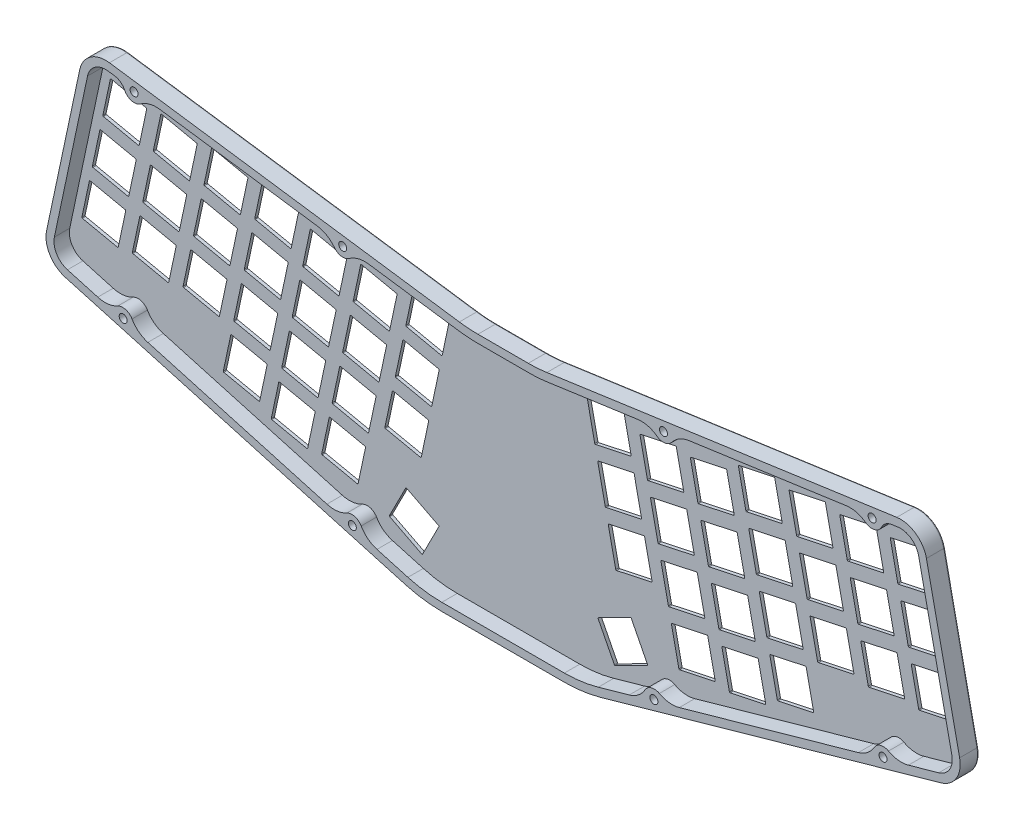
SolidWorks part; units mm, degrees
ref_plane "Front Plane" through (0, 0, 0) normal (0, 0, 1) x (1, 0, 0)
ref_plane "Top Plane" through (0, 0, 0) normal (0, 1, 0) x (1, 0, 0)
ref_plane "Right Plane" through (0, 0, 0) normal (1, 0, 0) x (0, 0, -1)
sketch "Model" plane through (0, 0, 0) normal (0, 0, 1) x (1, 0, 0)
  line L0 (325.3126, 39.9244) -> (319.5653, 66.9637)
  line L1 (325.3126, 39.9244) -> (332.0603, 8.179)
  line L2 (322.3782, 39.3007) -> (316.6308, 66.34)
  line L3 (322.3782, 39.3007) -> (329.1259, 7.5553)
  line L4 (306.4458, 71.4818) -> (308.8024, 71.8155)
  line L5 (13.8071, 71.4818) -> (11.4504, 71.8155)
  line L6 (-5.0598, 39.9244) -> (-11.8075, 8.179)
  line L7 (-2.1254, 39.3007) -> (-8.8731, 7.5553)
  line L8 (-5.0598, 39.9244) -> (0.6876, 66.9637)
  line L9 (-2.1254, 39.3007) -> (3.622, 66.34)
  line L10 (26.3327, -9.1816) -> (48.3039, -15.3856)
  line L11 (48.3039, -15.3856) -> (93.7705, -28.2242)
  line L12 (-3.9283, -0.6367) -> (7.4742, -3.8564)
  line L13 (90.0873, 60.6806) -> (30.9176, 69.0589)
  line L14 (210.7632, 57.9332) -> (177.0346, 53.1572)
  line L15 (169.604, 52.6338) -> (150.6488, 52.6338)
  line L16 (143.2182, 53.1572) -> (109.4896, 57.9332)
  line L17 (289.3352, 69.0589) -> (230.1656, 60.6806)
  line L18 (312.7787, -3.8564) -> (324.1811, -0.6367)
  line L19 (226.4824, -28.2242) -> (271.949, -15.3856)
  line L20 (271.949, -15.3856) -> (293.9202, -9.1816)
  line L21 (112.629, -33.5493) -> (124.2783, -36.8388)
  line L22 (137.0504, -38.6074) -> (160.1264, -38.6074)
  line L23 (160.1264, -38.6074) -> (183.2025, -38.6074)
  line L24 (195.9746, -36.8388) -> (207.6239, -33.5493)
  line L25 (169.604, 55.6338) -> (150.6488, 55.6338)
  line L26 (308.3818, 74.7858) -> (176.614, 56.1276)
  line L27 (272.7642, -18.2727) -> (324.9963, -3.5238)
  line L28 (196.7898, -39.7259) -> (272.7642, -18.2727)
  line L29 (160.1264, -41.6074) -> (183.2025, -41.6074)
  line L30 (137.0504, -41.6074) -> (160.1264, -41.6074)
  line L31 (47.4886, -18.2727) -> (123.463, -39.7259)
  line L32 (-4.7435, -3.5238) -> (47.4886, -18.2727)
  line L33 (143.6388, 56.1276) -> (11.8711, 74.7858)
  line L34 (196.5845, -32.4293) -> (202.5988, -29.3648)
  line L35 (190.1194, -20.2914) -> (196.2483, -32.32)
  line L36 (202.2573, -13.8263) -> (190.2287, -19.9552)
  line L37 (208.7224, -25.9641) -> (202.5935, -13.9355)
  line L38 (202.5988, -29.3648) -> (208.6131, -26.3004)
  line L39 (234.2278, -18.5408) -> (231.421, -5.3358)
  line L40 (220.8303, -21.6441) -> (234.0353, -18.8373)
  line L41 (217.7269, -8.2465) -> (220.5338, -21.4515)
  line L42 (231.1245, -5.1432) -> (217.9195, -7.95)
  line L43 (253.2284, -16.5467) -> (250.4216, -3.3417)
  line L44 (239.8309, -19.6501) -> (253.0359, -16.8433)
  line L45 (236.7276, -6.2525) -> (239.5344, -19.4575)
  line L46 (250.1251, -3.1492) -> (236.9201, -5.956)
  line L47 (210.4452, 1.9626) -> (207.6384, 15.1676)
  line L48 (197.0477, -1.1407) -> (210.2527, 1.6661)
  line L49 (193.9443, 12.2568) -> (196.7512, -0.9482)
  line L50 (207.3419, 15.3602) -> (194.1369, 12.5533)
  line L51 (206.4949, 20.5474) -> (203.6881, 33.7524)
  line L52 (193.0973, 17.4441) -> (206.3023, 20.2509)
  line L53 (189.994, 30.8416) -> (192.8008, 17.6366)
  line L54 (203.3916, 33.945) -> (190.1866, 31.1382)
  line L55 (202.5446, 39.1322) -> (199.7378, 52.3372)
  line L56 (189.147, 36.0289) -> (202.352, 38.8357)
  line L57 (186.0437, 49.4264) -> (188.8505, 36.2214)
  line L58 (199.4413, 52.5298) -> (186.2363, 49.723)
  line L59 (230.2775, 0.044) -> (227.4707, 13.249)
  line L60 (216.8799, -3.0593) -> (230.0849, -0.2525)
  line L61 (213.7766, 10.3383) -> (216.5834, -2.8667)
  line L62 (227.1742, 13.4416) -> (213.9692, 10.6348)
  line L63 (226.3272, 18.6288) -> (223.5204, 31.8338)
  line L64 (212.9296, 15.5255) -> (226.1346, 18.3323)
  line L65 (209.8263, 28.9231) -> (212.6331, 15.7181)
  line L66 (223.2239, 32.0264) -> (210.0189, 29.2196)
  line L67 (222.3769, 37.2136) -> (219.57, 50.4186)
  line L68 (208.9793, 34.1103) -> (222.1843, 36.9171)
  line L69 (205.876, 47.5079) -> (208.6828, 34.3029)
  line L70 (219.2735, 50.6112) -> (206.0685, 47.8044)
  line L71 (249.2781, 2.0381) -> (246.4713, 15.2431)
  line L72 (235.8806, -1.0653) -> (249.0856, 1.7416)
  line L73 (232.7772, 12.3323) -> (235.5841, -0.8727)
  line L74 (246.1748, 15.4356) -> (232.9698, 12.6288)
  line L75 (245.3278, 20.6229) -> (242.521, 33.8279)
  line L76 (231.9302, 17.5195) -> (245.1352, 20.3264)
  line L77 (228.8269, 30.9171) -> (231.6337, 17.7121)
  line L78 (242.2245, 34.0204) -> (229.0195, 31.2136)
  line L79 (241.3775, 39.2077) -> (238.5707, 52.4127)
  line L80 (227.9799, 36.1044) -> (241.1849, 38.9112)
  line L81 (224.8766, 49.5019) -> (227.6834, 36.2969)
  line L82 (238.2742, 52.6052) -> (225.0692, 49.7984)
  line L83 (271.2935, -10.151) -> (268.4867, 3.0539)
  line L84 (257.8959, -13.2544) -> (271.1009, -10.4476)
  line L85 (254.7926, 0.1432) -> (257.5994, -13.0618)
  line L86 (268.1901, 3.2465) -> (254.9852, 0.4397)
  line L87 (267.3431, 8.4338) -> (264.5363, 21.6387)
  line L88 (253.9456, 5.3304) -> (267.1506, 8.1372)
  line L89 (250.8423, 18.728) -> (253.6491, 5.523)
  line L90 (264.2398, 21.8313) -> (251.0348, 19.0245)
  line L91 (263.3928, 27.0186) -> (260.586, 40.2236)
  line L92 (249.9953, 23.9152) -> (263.2003, 26.722)
  line L93 (246.892, 37.3128) -> (249.6988, 24.1078)
  line L94 (260.2895, 40.4161) -> (247.0845, 37.6093)
  line L95 (259.4425, 45.6034) -> (256.6357, 58.8084)
  line L96 (246.045, 42.5) -> (259.2499, 45.3069)
  line L97 (242.9416, 55.8976) -> (245.7484, 42.6926)
  line L98 (256.3392, 59.0009) -> (243.1342, 56.1941)
  line L99 (286.4477, 9.9387) -> (283.6409, 23.1437)
  line L100 (273.0502, 6.8354) -> (286.2552, 9.6422)
  line L101 (269.9469, 20.2329) -> (272.7537, 7.0279)
  line L102 (283.3444, 23.3363) -> (270.1394, 20.5295)
  line L103 (282.4974, 28.5235) -> (279.6906, 41.7285)
  line L104 (269.0999, 25.4202) -> (282.3049, 28.227)
  line L105 (265.9965, 38.8177) -> (268.8033, 25.6128)
  line L106 (279.3941, 41.9211) -> (266.1891, 39.1143)
  line L107 (278.5471, 47.1083) -> (275.7403, 60.3133)
  line L108 (265.1495, 44.005) -> (278.3545, 46.8118)
  line L109 (262.0462, 57.4025) -> (264.853, 44.1976)
  line L110 (275.4438, 60.5059) -> (262.2388, 57.6991)
  line L111 (305.5523, 11.4437) -> (302.7455, 24.6487)
  line L112 (292.1548, 8.3403) -> (305.3598, 11.1471)
  line L113 (289.0514, 21.7379) -> (291.8582, 8.5329)
  line L114 (302.449, 24.8412) -> (289.244, 22.0344)
  line L115 (301.602, 30.0285) -> (298.7952, 43.2335)
  line L116 (288.2044, 26.9251) -> (301.4094, 29.732)
  line L117 (285.1011, 40.3227) -> (287.9079, 27.1177)
  line L118 (298.4987, 43.426) -> (285.2937, 40.6192)
  line L119 (297.6517, 48.6133) -> (294.8449, 61.8183)
  line L120 (284.2541, 45.5099) -> (297.4591, 48.3168)
  line L121 (281.1508, 58.9075) -> (283.9576, 45.7025)
  line L122 (294.5483, 62.0108) -> (281.3434, 59.204)
  line L123 (324.5529, 13.4377) -> (321.7461, 26.6427)
  line L124 (311.1554, 10.3344) -> (324.3604, 13.1412)
  line L125 (308.0521, 23.7319) -> (310.8589, 10.5269)
  line L126 (321.4496, 26.8352) -> (308.2446, 24.0284)
  line L127 (320.6026, 32.0225) -> (317.7958, 45.2275)
  line L128 (307.2051, 28.9192) -> (320.4101, 31.726)
  line L129 (304.1017, 42.3167) -> (306.9086, 29.1117)
  line L130 (317.4993, 45.42) -> (304.2943, 42.6132)
  line L131 (316.6523, 50.6073) -> (313.8455, 63.8123)
  line L132 (313.549, 64.0049) -> (300.344, 61.198)
  line L133 (300.1514, 60.9015) -> (302.9582, 47.6965)
  line L134 (303.2547, 47.504) -> (316.4597, 50.3108)
  line L135 (123.6683, -32.4293) -> (117.654, -29.3648)
  line L136 (130.1334, -20.2914) -> (124.0045, -32.32)
  line L137 (117.9956, -13.8263) -> (130.0242, -19.9552)
  line L138 (111.5305, -25.9641) -> (117.6593, -13.9355)
  line L139 (117.654, -29.3648) -> (111.6397, -26.3004)
  line L140 (86.025, -18.5408) -> (88.8318, -5.3358)
  line L141 (99.4226, -21.6441) -> (86.2176, -18.8373)
  line L142 (102.5259, -8.2465) -> (99.7191, -21.4515)
  line L143 (89.1283, -5.1432) -> (102.3333, -7.95)
  line L144 (67.0244, -16.5467) -> (69.8312, -3.3417)
  line L145 (80.4219, -19.6501) -> (67.2169, -16.8433)
  line L146 (83.5253, -6.2525) -> (80.7184, -19.4575)
  line L147 (70.1277, -3.1492) -> (83.3327, -5.956)
  line L148 (109.8076, 1.9626) -> (112.6144, 15.1676)
  line L149 (123.2052, -1.1407) -> (110.0002, 1.6661)
  line L150 (126.3085, 12.2568) -> (123.5017, -0.9482)
  line L151 (112.9109, 15.3602) -> (126.1159, 12.5533)
  line L152 (113.7579, 20.5474) -> (116.5647, 33.7524)
  line L153 (127.1555, 17.4441) -> (113.9505, 20.2509)
  line L154 (130.2588, 30.8416) -> (127.452, 17.6366)
  line L155 (116.8613, 33.945) -> (130.0662, 31.1382)
  line L156 (117.7083, 39.1322) -> (120.5151, 52.3372)
  line L157 (131.1058, 36.0289) -> (117.9008, 38.8357)
  line L158 (134.2091, 49.4264) -> (131.4023, 36.2214)
  line L159 (120.8116, 52.5298) -> (134.0166, 49.723)
  line L160 (89.9753, 0.044) -> (92.7821, 13.249)
  line L161 (103.3729, -3.0593) -> (90.1679, -0.2525)
  line L162 (106.4762, 10.3383) -> (103.6694, -2.8667)
  line L163 (93.0787, 13.4416) -> (106.2836, 10.6348)
  line L164 (93.9257, 18.6288) -> (96.7325, 31.8338)
  line L165 (107.3232, 15.5255) -> (94.1182, 18.3323)
  line L166 (110.4265, 28.9231) -> (107.6197, 15.7181)
  line L167 (97.029, 32.0264) -> (110.234, 29.2196)
  line L168 (97.876, 37.2136) -> (100.6828, 50.4186)
  line L169 (111.2735, 34.1103) -> (98.0685, 36.9171)
  line L170 (114.3769, 47.5079) -> (111.57, 34.3029)
  line L171 (100.9793, 50.6112) -> (114.1843, 47.8044)
  line L172 (70.9747, 2.0381) -> (73.7815, 15.2431)
  line L173 (84.3723, -1.0653) -> (71.1673, 1.7416)
  line L174 (87.4756, 12.3323) -> (84.6688, -0.8727)
  line L175 (74.078, 15.4356) -> (87.283, 12.6288)
  line L176 (74.925, 20.6229) -> (77.7318, 33.8279)
  line L177 (88.3226, 17.5195) -> (75.1176, 20.3264)
  line L178 (91.4259, 30.9171) -> (88.6191, 17.7121)
  line L179 (78.0284, 34.0204) -> (91.2333, 31.2136)
  line L180 (78.8753, 39.2077) -> (81.6822, 52.4127)
  line L181 (92.2729, 36.1044) -> (79.0679, 38.9112)
  line L182 (95.3762, 49.5019) -> (92.5694, 36.2969)
  line L183 (81.9787, 52.6052) -> (95.1837, 49.7984)
  line L184 (48.9594, -10.151) -> (51.7662, 3.0539)
  line L185 (62.3569, -13.2544) -> (49.1519, -10.4476)
  line L186 (65.4602, 0.1432) -> (62.6534, -13.0618)
  line L187 (52.0627, 3.2465) -> (65.2677, 0.4397)
  line L188 (52.9097, 8.4338) -> (55.7165, 21.6387)
  line L189 (66.3072, 5.3304) -> (53.1022, 8.1372)
  line L190 (69.4106, 18.728) -> (66.6037, 5.523)
  line L191 (56.013, 21.8313) -> (69.218, 19.0245)
  line L192 (56.86, 27.0186) -> (59.6668, 40.2236)
  line L193 (70.2576, 23.9152) -> (57.0526, 26.722)
  line L194 (73.3609, 37.3128) -> (70.5541, 24.1078)
  line L195 (59.9633, 40.4161) -> (73.1683, 37.6093)
  line L196 (60.8103, 45.6034) -> (63.6171, 58.8084)
  line L197 (74.2079, 42.5) -> (61.0029, 45.3069)
  line L198 (77.3112, 55.8976) -> (74.5044, 42.6926)
  line L199 (63.9136, 59.0009) -> (77.1186, 56.1941)
  line L200 (33.8051, 9.9387) -> (36.6119, 23.1437)
  line L201 (47.2026, 6.8354) -> (33.9977, 9.6422)
  line L202 (50.306, 20.2329) -> (47.4992, 7.0279)
  line L203 (36.9084, 23.3363) -> (50.1134, 20.5295)
  line L204 (37.7554, 28.5235) -> (40.5622, 41.7285)
  line L205 (51.153, 25.4202) -> (37.948, 28.227)
  line L206 (54.2563, 38.8177) -> (51.4495, 25.6128)
  line L207 (40.8587, 41.9211) -> (54.0637, 39.1143)
  line L208 (41.7057, 47.1083) -> (44.5125, 60.3133)
  line L209 (55.1033, 44.005) -> (41.8983, 46.8118)
  line L210 (58.2066, 57.4025) -> (55.3998, 44.1976)
  line L211 (44.8091, 60.5059) -> (58.0141, 57.6991)
  line L212 (14.7005, 11.4437) -> (17.5073, 24.6487)
  line L213 (28.0981, 8.3403) -> (14.8931, 11.1471)
  line L214 (31.2014, 21.7379) -> (28.3946, 8.5329)
  line L215 (17.8038, 24.8412) -> (31.0088, 22.0344)
  line L216 (18.6508, 30.0285) -> (21.4576, 43.2335)
  line L217 (32.0484, 26.9251) -> (18.8434, 29.732)
  line L218 (35.1517, 40.3227) -> (32.3449, 27.1177)
  line L219 (21.7542, 43.426) -> (34.9592, 40.6192)
  line L220 (22.6012, 48.6133) -> (25.408, 61.8183)
  line L221 (35.9987, 45.5099) -> (22.7937, 48.3168)
  line L222 (39.102, 58.9075) -> (36.2952, 45.7025)
  line L223 (25.7045, 62.0108) -> (38.9095, 59.204)
  line L224 (-4.3001, 13.4377) -> (-1.4933, 26.6427)
  line L225 (9.0974, 10.3344) -> (-4.1076, 13.1412)
  line L226 (12.2008, 23.7319) -> (9.394, 10.5269)
  line L227 (-1.1968, 26.8352) -> (12.0082, 24.0284)
  line L228 (-0.3498, 32.0225) -> (2.457, 45.2275)
  line L229 (13.0478, 28.9192) -> (-0.1572, 31.726)
  line L230 (16.1511, 42.3167) -> (13.3443, 29.1117)
  line L231 (2.7535, 45.42) -> (15.9585, 42.6132)
  line L232 (3.6005, 50.6073) -> (6.4073, 63.8123)
  line L233 (6.7039, 64.0049) -> (19.9088, 61.198)
  line L234 (20.1014, 60.9015) -> (17.2946, 47.6965)
  line L235 (16.9981, 47.504) -> (3.7931, 50.3108)
  circle A0 centre (21.1464, 69.9376) radius 1.5
  circle A1 centre (299.1065, 69.9376) radius 1.5
  arc A2 (296.6652, 67.2112) -> (289.3352, 69.0589) centre (290.7372, 59.1577) ccw
  arc A3 (306.4458, 71.4818) -> (302.641, 68.6986) centre (307.1468, 66.5312) ccw
  arc A4 (17.6118, 68.6986) -> (13.8071, 71.4818) centre (13.106, 66.5312) ccw
  arc A5 (30.9176, 69.0589) -> (23.5876, 67.2112) centre (29.5156, 59.1577) ccw
  arc A6 (17.6118, 68.6986) -> (23.5876, 67.2112) centre (21.2165, 70.4326) ccw
  arc A7 (296.6652, 67.2112) -> (302.641, 68.6986) centre (299.0364, 70.4326) ccw
  arc A8 (324.9963, -3.5238) -> (332.0603, 8.179) centre (322.2789, 6.0999) ccw
  arc A9 (319.5653, 66.9637) -> (308.3818, 74.7858) centre (309.7838, 64.8846) ccw
  arc A10 (324.1811, -0.6367) -> (329.1259, 7.5553) centre (322.2789, 6.0999) ccw
  arc A11 (316.6308, 66.34) -> (308.8024, 71.8155) centre (309.7838, 64.8846) ccw
  arc A12 (11.8711, 74.7858) -> (0.6876, 66.9637) centre (10.469, 64.8846) ccw
  arc A13 (-11.8075, 8.179) -> (-4.7435, -3.5238) centre (-2.026, 6.0999) ccw
  arc A14 (-8.8731, 7.5553) -> (-3.9283, -0.6367) centre (-2.026, 6.0999) ccw
  arc A15 (11.4504, 71.8155) -> (3.622, 66.34) centre (10.469, 64.8846) ccw
  circle A16 centre (303.2135, -6.0378) radius 1.5
  circle A17 centre (17.0393, -6.0378) radius 1.5
  arc A18 (293.9202, -9.1816) -> (299.8789, -4.5301) centre (291.2027, 0.4421) ccw
  arc A19 (305.2671, -3.0086) -> (312.7787, -3.8564) centre (310.0612, 5.7673) ccw
  arc A20 (20.3739, -4.5301) -> (26.3327, -9.1816) centre (29.0501, 0.4421) ccw
  arc A21 (7.4742, -3.8564) -> (14.9858, -3.0086) centre (10.1916, 5.7673) ccw
  arc A22 (20.3739, -4.5301) -> (14.9858, -3.0086) centre (16.9034, -6.519) ccw
  arc A23 (305.2671, -3.0086) -> (299.8789, -4.5301) centre (303.3494, -6.519) ccw
  circle A24 centre (220.5345, 58.8118) radius 1.5
  circle A25 centre (99.7183, 58.8118) radius 1.5
  arc A26 (230.1656, 60.6806) -> (223.6367, 56.8704) centre (231.5676, 50.7793) ccw
  arc A27 (218.0932, 56.0855) -> (210.7632, 57.9332) centre (212.1652, 48.032) ccw
  arc A28 (96.6161, 56.8704) -> (90.0873, 60.6806) centre (88.6852, 50.7793) ccw
  arc A29 (109.4896, 57.9332) -> (102.1596, 56.0855) centre (108.0876, 48.032) ccw
  arc A30 (218.0932, 56.0855) -> (223.6367, 56.8704) centre (220.4644, 59.3069) ccw
  arc A31 (96.6161, 56.8704) -> (102.1596, 56.0855) centre (99.7884, 59.3069) ccw
  circle A32 centre (216.9173, -30.4056) radius 1.5
  arc A33 (218.9708, -27.3764) -> (226.4824, -28.2242) centre (223.7649, -18.6005) ccw
  arc A34 (207.6239, -33.5493) -> (213.5826, -28.8979) centre (204.9064, -23.9256) ccw
  circle A35 centre (103.3356, -30.4056) radius 1.5
  arc A36 (106.6702, -28.8979) -> (112.629, -33.5493) centre (115.3464, -23.9256) ccw
  arc A37 (93.7705, -28.2242) -> (101.2821, -27.3764) centre (96.4879, -18.6005) ccw
  arc A38 (218.9708, -27.3764) -> (213.5826, -28.8979) centre (217.0531, -30.8868) ccw
  arc A39 (106.6702, -28.8979) -> (101.2821, -27.3764) centre (103.1997, -30.8868) ccw
  arc A40 (169.604, 55.6338) -> (176.614, 56.1276) centre (169.604, 105.6338) ccw
  arc A41 (183.2025, -41.6074) -> (196.7898, -39.7259) centre (183.2025, 8.3926) ccw
  arc A42 (123.463, -39.7259) -> (137.0504, -41.6074) centre (137.0504, 8.3926) ccw
  arc A43 (143.6388, 56.1276) -> (150.6488, 55.6338) centre (150.6488, 105.6338) ccw
  arc A44 (196.2483, -32.32) -> (196.5845, -32.4293) centre (196.471, -32.2065) ccw
  arc A45 (190.2287, -19.9552) -> (190.1194, -20.2914) centre (190.3422, -20.1779) ccw
  arc A46 (202.5935, -13.9355) -> (202.2573, -13.8263) centre (202.3708, -14.049) ccw
  arc A47 (208.6131, -26.3004) -> (208.7224, -25.9641) centre (208.4996, -26.0776) ccw
  arc A48 (231.421, -5.3358) -> (231.1245, -5.1432) centre (231.1765, -5.3878) ccw
  arc A49 (217.9195, -7.95) -> (217.7269, -8.2465) centre (217.9715, -8.1946) ccw
  arc A50 (220.5338, -21.4515) -> (220.8303, -21.6441) centre (220.7783, -21.3996) ccw
  arc A51 (234.0353, -18.8373) -> (234.2278, -18.5408) centre (233.9833, -18.5927) ccw
  arc A52 (250.4216, -3.3417) -> (250.1251, -3.1492) centre (250.1771, -3.3937) ccw
  arc A53 (236.9201, -5.956) -> (236.7276, -6.2525) centre (236.9721, -6.2005) ccw
  arc A54 (239.5344, -19.4575) -> (239.8309, -19.6501) centre (239.7789, -19.4055) ccw
  arc A55 (253.0359, -16.8433) -> (253.2284, -16.5467) centre (252.9839, -16.5987) ccw
  arc A56 (207.6384, 15.1676) -> (207.3419, 15.3602) centre (207.3939, 15.1156) ccw
  arc A57 (194.1369, 12.5533) -> (193.9443, 12.2568) centre (194.1889, 12.3088) ccw
  arc A58 (196.7512, -0.9482) -> (197.0477, -1.1407) centre (196.9957, -0.8962) ccw
  arc A59 (210.2527, 1.6661) -> (210.4452, 1.9626) centre (210.2007, 1.9106) ccw
  arc A60 (203.6881, 33.7524) -> (203.3916, 33.945) centre (203.4436, 33.7004) ccw
  arc A61 (190.1866, 31.1382) -> (189.994, 30.8416) centre (190.2386, 30.8936) ccw
  arc A62 (192.8008, 17.6366) -> (193.0973, 17.4441) centre (193.0454, 17.6886) ccw
  arc A63 (206.3023, 20.2509) -> (206.4949, 20.5474) centre (206.2504, 20.4954) ccw
  arc A64 (199.7378, 52.3372) -> (199.4413, 52.5298) centre (199.4932, 52.2852) ccw
  arc A65 (186.2363, 49.723) -> (186.0437, 49.4264) centre (186.2882, 49.4784) ccw
  arc A66 (188.8505, 36.2214) -> (189.147, 36.0289) centre (189.095, 36.2734) ccw
  arc A67 (202.352, 38.8357) -> (202.5446, 39.1322) centre (202.3, 39.0802) ccw
  arc A68 (227.4707, 13.249) -> (227.1742, 13.4416) centre (227.2262, 13.1971) ccw
  arc A69 (213.9692, 10.6348) -> (213.7766, 10.3383) centre (214.0212, 10.3902) ccw
  arc A70 (216.5834, -2.8667) -> (216.8799, -3.0593) centre (216.828, -2.8147) ccw
  arc A71 (230.0849, -0.2525) -> (230.2775, 0.044) centre (230.033, -0.0079) ccw
  arc A72 (223.5204, 31.8338) -> (223.2239, 32.0264) centre (223.2758, 31.7819) ccw
  arc A73 (210.0189, 29.2196) -> (209.8263, 28.9231) centre (210.0708, 28.9751) ccw
  arc A74 (212.6331, 15.7181) -> (212.9296, 15.5255) centre (212.8776, 15.7701) ccw
  arc A75 (226.1346, 18.3323) -> (226.3272, 18.6288) centre (226.0826, 18.5769) ccw
  arc A76 (219.57, 50.4186) -> (219.2735, 50.6112) centre (219.3255, 50.3667) ccw
  arc A77 (206.0685, 47.8044) -> (205.876, 47.5079) centre (206.1205, 47.5599) ccw
  arc A78 (208.6828, 34.3029) -> (208.9793, 34.1103) centre (208.9273, 34.3549) ccw
  arc A79 (222.1843, 36.9171) -> (222.3769, 37.2136) centre (222.1323, 37.1617) ccw
  arc A80 (246.4713, 15.2431) -> (246.1748, 15.4356) centre (246.2268, 15.1911) ccw
  arc A81 (249.0856, 1.7416) -> (249.2781, 2.0381) centre (249.0336, 1.9861) ccw
  arc A82 (232.9698, 12.6288) -> (232.7772, 12.3323) centre (233.0218, 12.3843) ccw
  arc A83 (235.5841, -0.8727) -> (235.8806, -1.0653) centre (235.8286, -0.8207) ccw
  arc A84 (242.521, 33.8279) -> (242.2245, 34.0204) centre (242.2765, 33.7759) ccw
  arc A85 (229.0195, 31.2136) -> (228.8269, 30.9171) centre (229.0715, 30.9691) ccw
  arc A86 (231.6337, 17.7121) -> (231.9302, 17.5195) centre (231.8783, 17.7641) ccw
  arc A87 (245.1352, 20.3264) -> (245.3278, 20.6229) centre (245.0833, 20.5709) ccw
  arc A88 (238.5707, 52.4127) -> (238.2742, 52.6052) centre (238.3261, 52.3607) ccw
  arc A89 (225.0692, 49.7984) -> (224.8766, 49.5019) centre (225.1211, 49.5539) ccw
  arc A90 (227.6834, 36.2969) -> (227.9799, 36.1044) centre (227.9279, 36.3489) ccw
  arc A91 (241.1849, 38.9112) -> (241.3775, 39.2077) centre (241.1329, 39.1557) ccw
  arc A92 (268.4867, 3.0539) -> (268.1901, 3.2465) centre (268.2421, 3.002) ccw
  arc A93 (254.9852, 0.4397) -> (254.7926, 0.1432) centre (255.0371, 0.1952) ccw
  arc A94 (257.5994, -13.0618) -> (257.8959, -13.2544) centre (257.8439, -13.0098) ccw
  arc A95 (271.1009, -10.4476) -> (271.2935, -10.151) centre (271.0489, -10.203) ccw
  arc A96 (264.5363, 21.6387) -> (264.2398, 21.8313) centre (264.2918, 21.5868) ccw
  arc A97 (251.0348, 19.0245) -> (250.8423, 18.728) centre (251.0868, 18.78) ccw
  arc A98 (253.6491, 5.523) -> (253.9456, 5.3304) centre (253.8936, 5.575) ccw
  arc A99 (267.1506, 8.1372) -> (267.3431, 8.4338) centre (267.0986, 8.3818) ccw
  arc A100 (260.586, 40.2236) -> (260.2895, 40.4161) centre (260.3415, 40.1716) ccw
  arc A101 (247.0845, 37.6093) -> (246.892, 37.3128) centre (247.1365, 37.3648) ccw
  arc A102 (249.6988, 24.1078) -> (249.9953, 23.9152) centre (249.9433, 24.1598) ccw
  arc A103 (263.2003, 26.722) -> (263.3928, 27.0186) centre (263.1483, 26.9666) ccw
  arc A104 (256.6357, 58.8084) -> (256.3392, 59.0009) centre (256.3912, 58.7564) ccw
  arc A105 (243.1342, 56.1941) -> (242.9416, 55.8976) centre (243.1862, 55.9496) ccw
  arc A106 (245.7484, 42.6926) -> (246.045, 42.5) centre (245.993, 42.7446) ccw
  arc A107 (259.2499, 45.3069) -> (259.4425, 45.6034) centre (259.198, 45.5514) ccw
  arc A108 (283.6409, 23.1437) -> (283.3444, 23.3363) centre (283.3964, 23.0917) ccw
  arc A109 (270.1394, 20.5295) -> (269.9469, 20.2329) centre (270.1914, 20.2849) ccw
  arc A110 (272.7537, 7.0279) -> (273.0502, 6.8354) centre (272.9982, 7.0799) ccw
  arc A111 (286.2552, 9.6422) -> (286.4477, 9.9387) centre (286.2032, 9.8867) ccw
  arc A112 (279.6906, 41.7285) -> (279.3941, 41.9211) centre (279.4461, 41.6765) ccw
  arc A113 (266.1891, 39.1143) -> (265.9965, 38.8177) centre (266.2411, 38.8697) ccw
  arc A114 (268.8033, 25.6128) -> (269.0999, 25.4202) centre (269.0479, 25.6647) ccw
  arc A115 (282.3049, 28.227) -> (282.4974, 28.5235) centre (282.2529, 28.4715) ccw
  arc A116 (275.7403, 60.3133) -> (275.4438, 60.5059) centre (275.4957, 60.2613) ccw
  arc A117 (262.2388, 57.6991) -> (262.0462, 57.4025) centre (262.2908, 57.4545) ccw
  arc A118 (264.853, 44.1976) -> (265.1495, 44.005) centre (265.0976, 44.2495) ccw
  arc A119 (278.3545, 46.8118) -> (278.5471, 47.1083) centre (278.3026, 47.0563) ccw
  arc A120 (302.7455, 24.6487) -> (302.449, 24.8412) centre (302.501, 24.5967) ccw
  arc A121 (305.3598, 11.1471) -> (305.5523, 11.4437) centre (305.3078, 11.3917) ccw
  arc A122 (289.244, 22.0344) -> (289.0514, 21.7379) centre (289.296, 21.7899) ccw
  arc A123 (291.8582, 8.5329) -> (292.1548, 8.3403) centre (292.1028, 8.5849) ccw
  arc A124 (298.7952, 43.2335) -> (298.4987, 43.426) centre (298.5506, 43.1815) ccw
  arc A125 (285.2937, 40.6192) -> (285.1011, 40.3227) centre (285.3457, 40.3747) ccw
  arc A126 (287.9079, 27.1177) -> (288.2044, 26.9251) centre (288.1525, 27.1697) ccw
  arc A127 (301.4094, 29.732) -> (301.602, 30.0285) centre (301.3575, 29.9765) ccw
  arc A128 (294.8449, 61.8183) -> (294.5483, 62.0108) centre (294.6003, 61.7663) ccw
  arc A129 (281.3434, 59.204) -> (281.1508, 58.9075) centre (281.3953, 58.9595) ccw
  arc A130 (283.9576, 45.7025) -> (284.2541, 45.5099) centre (284.2021, 45.7545) ccw
  arc A131 (297.4591, 48.3168) -> (297.6517, 48.6133) centre (297.4071, 48.5613) ccw
  arc A132 (321.7461, 26.6427) -> (321.4496, 26.8352) centre (321.5016, 26.5907) ccw
  arc A133 (308.2446, 24.0284) -> (308.0521, 23.7319) centre (308.2966, 23.7839) ccw
  arc A134 (310.8589, 10.5269) -> (311.1554, 10.3344) centre (311.1034, 10.5789) ccw
  arc A135 (324.3604, 13.1412) -> (324.5529, 13.4377) centre (324.3084, 13.3857) ccw
  arc A136 (317.7958, 45.2275) -> (317.4993, 45.42) centre (317.5513, 45.1755) ccw
  arc A137 (306.9086, 29.1117) -> (307.2051, 28.9192) centre (307.1531, 29.1637) ccw
  arc A138 (320.4101, 31.726) -> (320.6026, 32.0225) centre (320.3581, 31.9705) ccw
  arc A139 (304.2943, 42.6132) -> (304.1017, 42.3167) centre (304.3463, 42.3687) ccw
  arc A140 (313.8455, 63.8123) -> (313.549, 64.0049) centre (313.601, 63.7603) ccw
  arc A141 (300.344, 61.198) -> (300.1514, 60.9015) centre (300.396, 60.9535) ccw
  arc A142 (316.4597, 50.3108) -> (316.6523, 50.6073) centre (316.4078, 50.5553) ccw
  arc A143 (302.9582, 47.6965) -> (303.2547, 47.504) centre (303.2028, 47.7485) ccw
  arc A144 (123.6683, -32.4293) -> (124.0045, -32.32) centre (123.7818, -32.2065) ccw
  arc A145 (130.1334, -20.2914) -> (130.0242, -19.9552) centre (129.9107, -20.1779) ccw
  arc A146 (117.9956, -13.8263) -> (117.6593, -13.9355) centre (117.8821, -14.049) ccw
  arc A147 (111.5305, -25.9641) -> (111.6397, -26.3004) centre (111.7532, -26.0776) ccw
  arc A148 (89.1283, -5.1432) -> (88.8318, -5.3358) centre (89.0764, -5.3878) ccw
  arc A149 (102.5259, -8.2465) -> (102.3333, -7.95) centre (102.2813, -8.1946) ccw
  arc A150 (99.4226, -21.6441) -> (99.7191, -21.4515) centre (99.4745, -21.3996) ccw
  arc A151 (86.025, -18.5408) -> (86.2176, -18.8373) centre (86.2695, -18.5927) ccw
  arc A152 (70.1277, -3.1492) -> (69.8312, -3.3417) centre (70.0757, -3.3937) ccw
  arc A153 (83.5253, -6.2525) -> (83.3327, -5.956) centre (83.2807, -6.2005) ccw
  arc A154 (80.4219, -19.6501) -> (80.7184, -19.4575) centre (80.4739, -19.4055) ccw
  arc A155 (67.0244, -16.5467) -> (67.2169, -16.8433) centre (67.2689, -16.5987) ccw
  arc A156 (112.9109, 15.3602) -> (112.6144, 15.1676) centre (112.859, 15.1156) ccw
  arc A157 (126.3085, 12.2568) -> (126.1159, 12.5533) centre (126.0639, 12.3088) ccw
  arc A158 (123.2052, -1.1407) -> (123.5017, -0.9482) centre (123.2571, -0.8962) ccw
  arc A159 (109.8076, 1.9626) -> (110.0002, 1.6661) centre (110.0521, 1.9106) ccw
  arc A160 (116.8613, 33.945) -> (116.5647, 33.7524) centre (116.8093, 33.7004) ccw
  arc A161 (130.2588, 30.8416) -> (130.0662, 31.1382) centre (130.0143, 30.8936) ccw
  arc A162 (127.1555, 17.4441) -> (127.452, 17.6366) centre (127.2075, 17.6886) ccw
  arc A163 (113.7579, 20.5474) -> (113.9505, 20.2509) centre (114.0025, 20.4954) ccw
  arc A164 (120.8116, 52.5298) -> (120.5151, 52.3372) centre (120.7596, 52.2852) ccw
  arc A165 (134.2091, 49.4264) -> (134.0166, 49.723) centre (133.9646, 49.4784) ccw
  arc A166 (131.1058, 36.0289) -> (131.4023, 36.2214) centre (131.1578, 36.2734) ccw
  arc A167 (117.7083, 39.1322) -> (117.9008, 38.8357) centre (117.9528, 39.0802) ccw
  arc A168 (93.0787, 13.4416) -> (92.7821, 13.249) centre (93.0267, 13.1971) ccw
  arc A169 (106.4762, 10.3383) -> (106.2836, 10.6348) centre (106.2317, 10.3902) ccw
  arc A170 (103.3729, -3.0593) -> (103.6694, -2.8667) centre (103.4249, -2.8147) ccw
  arc A171 (89.9753, 0.044) -> (90.1679, -0.2525) centre (90.2199, -0.0079) ccw
  arc A172 (97.029, 32.0264) -> (96.7325, 31.8338) centre (96.977, 31.7819) ccw
  arc A173 (110.4265, 28.9231) -> (110.234, 29.2196) centre (110.182, 28.9751) ccw
  arc A174 (107.3232, 15.5255) -> (107.6197, 15.7181) centre (107.3752, 15.7701) ccw
  arc A175 (93.9257, 18.6288) -> (94.1182, 18.3323) centre (94.1702, 18.5769) ccw
  arc A176 (100.9793, 50.6112) -> (100.6828, 50.4186) centre (100.9273, 50.3667) ccw
  arc A177 (114.3769, 47.5079) -> (114.1843, 47.8044) centre (114.1323, 47.5599) ccw
  arc A178 (111.2735, 34.1103) -> (111.57, 34.3029) centre (111.3255, 34.3549) ccw
  arc A179 (97.876, 37.2136) -> (98.0685, 36.9171) centre (98.1205, 37.1617) ccw
  arc A180 (74.078, 15.4356) -> (73.7815, 15.2431) centre (74.026, 15.1911) ccw
  arc A181 (70.9747, 2.0381) -> (71.1673, 1.7416) centre (71.2192, 1.9861) ccw
  arc A182 (87.4756, 12.3323) -> (87.283, 12.6288) centre (87.231, 12.3843) ccw
  arc A183 (84.3723, -1.0653) -> (84.6688, -0.8727) centre (84.4242, -0.8207) ccw
  arc A184 (78.0284, 34.0204) -> (77.7318, 33.8279) centre (77.9764, 33.7759) ccw
  arc A185 (91.4259, 30.9171) -> (91.2333, 31.2136) centre (91.1814, 30.9691) ccw
  arc A186 (88.3226, 17.5195) -> (88.6191, 17.7121) centre (88.3746, 17.7641) ccw
  arc A187 (74.925, 20.6229) -> (75.1176, 20.3264) centre (75.1696, 20.5709) ccw
  arc A188 (81.9787, 52.6052) -> (81.6822, 52.4127) centre (81.9267, 52.3607) ccw
  arc A189 (95.3762, 49.5019) -> (95.1837, 49.7984) centre (95.1317, 49.5539) ccw
  arc A190 (92.2729, 36.1044) -> (92.5694, 36.2969) centre (92.3249, 36.3489) ccw
  arc A191 (78.8753, 39.2077) -> (79.0679, 38.9112) centre (79.1199, 39.1557) ccw
  arc A192 (52.0627, 3.2465) -> (51.7662, 3.0539) centre (52.0107, 3.002) ccw
  arc A193 (65.4602, 0.1432) -> (65.2677, 0.4397) centre (65.2157, 0.1952) ccw
  arc A194 (62.3569, -13.2544) -> (62.6534, -13.0618) centre (62.4089, -13.0098) ccw
  arc A195 (48.9594, -10.151) -> (49.1519, -10.4476) centre (49.2039, -10.203) ccw
  arc A196 (56.013, 21.8313) -> (55.7165, 21.6387) centre (55.961, 21.5868) ccw
  arc A197 (69.4106, 18.728) -> (69.218, 19.0245) centre (69.166, 18.78) ccw
  arc A198 (66.3072, 5.3304) -> (66.6037, 5.523) centre (66.3592, 5.575) ccw
  arc A199 (52.9097, 8.4338) -> (53.1022, 8.1372) centre (53.1542, 8.3818) ccw
  arc A200 (59.9633, 40.4161) -> (59.6668, 40.2236) centre (59.9113, 40.1716) ccw
  arc A201 (73.3609, 37.3128) -> (73.1683, 37.6093) centre (73.1163, 37.3648) ccw
  arc A202 (70.2576, 23.9152) -> (70.5541, 24.1078) centre (70.3095, 24.1598) ccw
  arc A203 (56.86, 27.0186) -> (57.0526, 26.722) centre (57.1045, 26.9666) ccw
  arc A204 (63.9136, 59.0009) -> (63.6171, 58.8084) centre (63.8617, 58.7564) ccw
  arc A205 (77.3112, 55.8976) -> (77.1186, 56.1941) centre (77.0667, 55.9496) ccw
  arc A206 (74.2079, 42.5) -> (74.5044, 42.6926) centre (74.2599, 42.7446) ccw
  arc A207 (60.8103, 45.6034) -> (61.0029, 45.3069) centre (61.0549, 45.5514) ccw
  arc A208 (36.9084, 23.3363) -> (36.6119, 23.1437) centre (36.8564, 23.0917) ccw
  arc A209 (50.306, 20.2329) -> (50.1134, 20.5295) centre (50.0614, 20.2849) ccw
  arc A210 (47.2026, 6.8354) -> (47.4992, 7.0279) centre (47.2546, 7.0799) ccw
  arc A211 (33.8051, 9.9387) -> (33.9977, 9.6422) centre (34.0496, 9.8867) ccw
  arc A212 (40.8587, 41.9211) -> (40.5622, 41.7285) centre (40.8068, 41.6765) ccw
  arc A213 (54.2563, 38.8177) -> (54.0637, 39.1143) centre (54.0118, 38.8697) ccw
  arc A214 (51.153, 25.4202) -> (51.4495, 25.6128) centre (51.2049, 25.6647) ccw
  arc A215 (37.7554, 28.5235) -> (37.948, 28.227) centre (38, 28.4715) ccw
  arc A216 (44.8091, 60.5059) -> (44.5125, 60.3133) centre (44.7571, 60.2613) ccw
  arc A217 (58.2066, 57.4025) -> (58.0141, 57.6991) centre (57.9621, 57.4545) ccw
  arc A218 (55.1033, 44.005) -> (55.3998, 44.1976) centre (55.1553, 44.2495) ccw
  arc A219 (41.7057, 47.1083) -> (41.8983, 46.8118) centre (41.9503, 47.0563) ccw
  arc A220 (17.8038, 24.8412) -> (17.5073, 24.6487) centre (17.7519, 24.5967) ccw
  arc A221 (14.7005, 11.4437) -> (14.8931, 11.1471) centre (14.945, 11.3917) ccw
  arc A222 (31.2014, 21.7379) -> (31.0088, 22.0344) centre (30.9569, 21.7899) ccw
  arc A223 (28.0981, 8.3403) -> (28.3946, 8.5329) centre (28.15, 8.5849) ccw
  arc A224 (21.7542, 43.426) -> (21.4576, 43.2335) centre (21.7022, 43.1815) ccw
  arc A225 (35.1517, 40.3227) -> (34.9592, 40.6192) centre (34.9072, 40.3747) ccw
  arc A226 (32.0484, 26.9251) -> (32.3449, 27.1177) centre (32.1004, 27.1697) ccw
  arc A227 (18.6508, 30.0285) -> (18.8434, 29.732) centre (18.8954, 29.9765) ccw
  arc A228 (25.7045, 62.0108) -> (25.408, 61.8183) centre (25.6525, 61.7663) ccw
  arc A229 (39.102, 58.9075) -> (38.9095, 59.204) centre (38.8575, 58.9595) ccw
  arc A230 (35.9987, 45.5099) -> (36.2952, 45.7025) centre (36.0507, 45.7545) ccw
  arc A231 (22.6012, 48.6133) -> (22.7937, 48.3168) centre (22.8457, 48.5613) ccw
  arc A232 (-1.1968, 26.8352) -> (-1.4933, 26.6427) centre (-1.2488, 26.5907) ccw
  arc A233 (12.2008, 23.7319) -> (12.0082, 24.0284) centre (11.9562, 23.7839) ccw
  arc A234 (9.0974, 10.3344) -> (9.394, 10.5269) centre (9.1494, 10.5789) ccw
  arc A235 (-4.3001, 13.4377) -> (-4.1076, 13.1412) centre (-4.0556, 13.3857) ccw
  arc A236 (2.7535, 45.42) -> (2.457, 45.2275) centre (2.7016, 45.1755) ccw
  arc A237 (13.0478, 28.9192) -> (13.3443, 29.1117) centre (13.0997, 29.1637) ccw
  arc A238 (-0.3498, 32.0225) -> (-0.1572, 31.726) centre (-0.1053, 31.9705) ccw
  arc A239 (16.1511, 42.3167) -> (15.9585, 42.6132) centre (15.9065, 42.3687) ccw
  arc A240 (6.7039, 64.0049) -> (6.4073, 63.8123) centre (6.6519, 63.7603) ccw
  arc A241 (20.1014, 60.9015) -> (19.9088, 61.198) centre (19.8569, 60.9535) ccw
  arc A242 (3.6005, 50.6073) -> (3.7931, 50.3108) centre (3.8451, 50.5553) ccw
  arc A243 (16.9981, 47.504) -> (17.2946, 47.6965) centre (17.0501, 47.7485) ccw
  arc A244 (169.604, 52.6338) -> (177.0346, 53.1572) centre (169.604, 105.6338) ccw
  arc A245 (143.2182, 53.1572) -> (150.6488, 52.6338) centre (150.6488, 105.6338) ccw
  arc A246 (124.2783, -36.8388) -> (137.0504, -38.6074) centre (137.0504, 8.3926) ccw
  arc A247 (183.2025, -38.6074) -> (195.9746, -36.8388) centre (183.2025, 8.3926) ccw
extrude "Boss-Extrude1" add sketch "Model" along normal blind 7 contours A43 L33 A12 L8 L6 A13 L32 L31 A42 L30 L29 A41 L28 L27 A8 L1 L0 A9 L26 A40 L25 A247 L23 L22 A246 L21 A36 A39 A37 L11 L10 A20 A22 A21 L12 A14 L7 L9 A15 L5 A4 A6 A5 L13 A28 A31 A29 L16 A245 L15 region at (328.331, 23.9762, 0)
extrude "Boss-Extrude2" add sketch "Model<3>" along normal blind 1.2 contours L23 A247 L24 A34 A38 A33 L19 L20 A18 A23 A19 L18 A10 L3 L2 A11 L4 A3 A7 A2 L17 A26 A30 A27 L14 A244 L15 A245 L16 A29 A31 A28 L13 A5 A6 A4 L5 A15 L9 L7 A14 L12 A21 A22 A20 L10 L11 A37 A39 A36 L21 region at (160.1264, 15.5989, 0)
sketch "Model<3>" plane through (0, 0, 0) normal (0, 0, 1) x (1, 0, 0) same geometry as "Model"
extrude "Boss-Extrude3" add sketch "Model<4>" along normal blind 2 contours A35 | A17 | A0 | A25 | A32 | A24 | A16 | A1 region at (21.1464, 69.9376, 0) region at (299.1065, 69.9376, 0) region at (303.2135, -6.0378, 0) region at (17.0393, -6.0378, 0) region at (220.5345, 58.8118, 0) region at (99.7183, 58.8118, 0) region at (216.9173, -30.4056, 0) region at (103.3356, -30.4056, 0)
sketch "Model<4>" plane through (0, 0, 0) normal (0, 0, 1) x (1, 0, 0) same geometry as "Model"
fillet "Fillet1" radius 0.5 1 edges at (160.1264, -41.6074, 0) type face fillet first side face at (160.1264, 22.1313, 0) second side face at (160.1264, -41.6074, 3.5)
